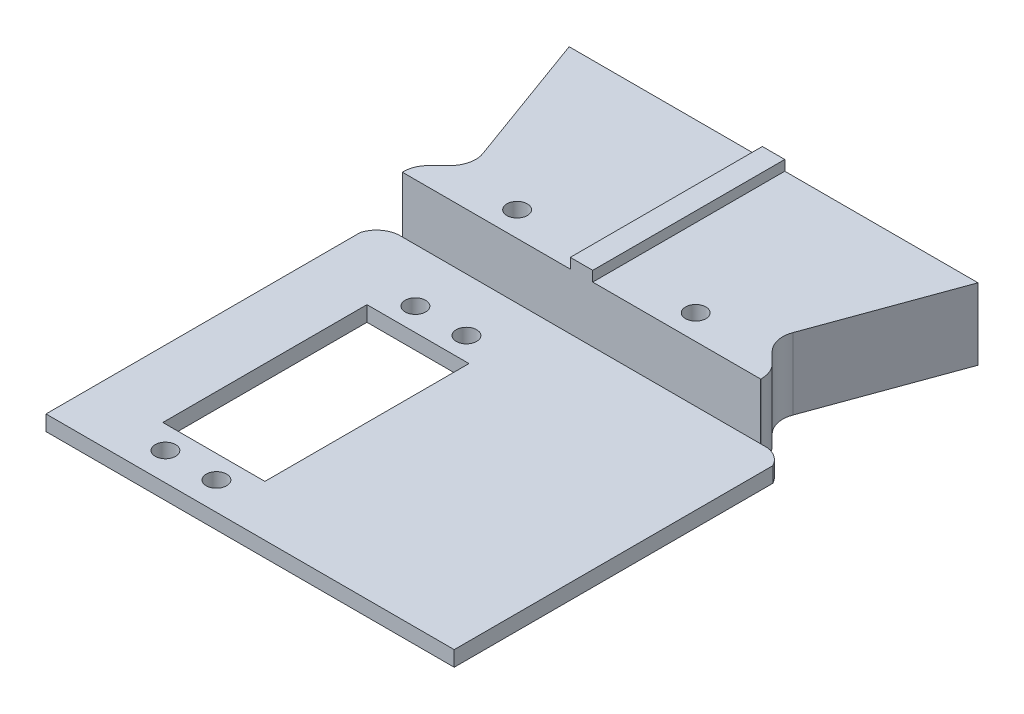
SolidWorks part; units mm, degrees
ref_plane "Front Plane" through (0, 0, 0) normal (0, 0, 1) x (1, 0, 0)
ref_plane "Top Plane" through (0, 0, 0) normal (0, 1, 0) x (1, 0, 0)
ref_plane "Right Plane" through (0, 0, 0) normal (1, 0, 0) x (0, 0, -1)
sketch "Sketch1" plane through (0, 0, 0) normal (0, 1, 0) x (1, 0, 0)
  line L0 (-17.5, 0) -> (17.5, 0) construction
  line L2 (-30.3893, 6.1749) -> (-40.0654, 32.76)
  line L3 (-40.0654, 32.76) -> (40.0654, 32.76)
  line L4 (40.0654, 32.76) -> (30.3893, 6.1749)
  line L5 (-35.1226, -23.3107) -> (-35.1226, -4.7122)
  line L6 (-35.1226, -23.3107) -> (35.1226, -23.3107)
  line L8 (-33.6581, -1.1767) -> (-31.5522, 0.9293)
  line L9 (35.1226, -23.3107) -> (35.1226, -4.7122)
  line L10 (33.6581, -1.1767) -> (31.5522, 0.9293)
  arc A2 (-31.5522, 0.9293) -> (-30.3893, 6.1749) centre (-35.0877, 4.4648) ccw
  arc A3 (-35.1226, -4.7122) -> (-33.6581, -1.1767) centre (-30.1226, -4.7122) cw
  arc A4 (35.1226, -4.7122) -> (33.6581, -1.1767) centre (30.1226, -4.7122) ccw
  arc A5 (31.5522, 0.9293) -> (30.3893, 6.1749) centre (35.0877, 4.4648) cw
  dimension "D5" = 5
  dimension "D6" = 5
  dimension "D7" = 18.5985
  dimension "D8" = 30.1226
  dimension "D19" = 5
  dimension "D20" = 5
  dimension "D1" = 35
  dimension "D2" = 17.5
  dimension "D3" = 23.3107
  dimension "D4" = 18.5985
  dimension "D9" = 30.1226
  dimension "D10" = 4.7122
  dimension "D11" = 5
  dimension "D12" = 32.76
  dimension "D13" = 70
  dimension "D14" = 70
  dimension "D15" = 28.2913
  dimension "D16" = 28.2913
  dimension "D17" = 2.9782
  dimension "D18" = 2.9782
extrude "Boss-Extrude1" add sketch "Sketch1" along normal blind 3
sketch "Sketch8" plane through (0, 3, 0) normal (0, 1, 0) x (1, 0, 0)
  line L0 (-35.1226, -23.3107) -> (35.1226, -23.3107) construction
  line L1 (-35.1226, -23.3107) -> (35.1226, -23.3107)
  line L2 (-35.1226, -23.3107) -> (-25.1226, -33.3107)
  line L3 (-25.1226, -33.3107) -> (25.1226, -33.3107)
  line L4 (25.1226, -33.3107) -> (35.1226, -23.3107)
  dimension "D1" = 10
  dimension "D2" = 45
  dimension "D3" = 45
extrude "Boss-Extrude5" add sketch "Sketch8" against normal blind 3
sketch "Croquis1" plane through (0, 3, 0) normal (0, 1, 0) x (1, 0, 0)
  line L0 (-40.0654, 32.76) -> (40.0654, 32.76) construction
  line L1 (0, 32.76) -> (0, 0) construction
  line L2 (0, 0) -> (-17.5, 0) construction
  line L3 (0, 0) -> (17.5, 0) construction
  circle A0 centre (-17.5, 0) radius 2
  circle A1 centre (17.5, 0) radius 2
  dimension "D4" = 4
  dimension "D5" = 4
  dimension "D1" = 32.76
  dimension "D2" = 17.5
  dimension "D3" = 17.5
extrude "Cortar-Extruir1" cut sketch "Croquis1" against normal blind 10
sketch "Croquis2" plane through (0, 3, 0) normal (0, 1, 0) x (1, 0, 0)
  line L1 (17, -36.0007) -> (40.0026, -36.0007)
  line L2 (40.0026, -36.0007) -> (40.0026, -33.0007)
  line L7 (17, -36.0007) -> (-40, -36.0007)
  line L8 (-40, -36.0007) -> (-40, -4.8773)
  line L9 (-40, -4.8773) -> (40.0026, -4.8773)
  line L10 (40.0026, -4.8773) -> (40.0026, -33.0007)
  line L13 (35.1226, -23.3107) -> (35.1226, -4.7122) construction
  dimension "D6" = 4.88
extrude "Saliente-Extruir1" add sketch "Croquis2" against normal up to surface (3 mm away) up to face at (-17.5, 0, 2)
sketch "Croquis3" plane through (0, 3, 0) normal (0, 1, 0) x (1, 0, 0)
  line L0 (-40, -4.8773) -> (-40, -36.0007) construction
  line L2 (40.0026, -36.0007) -> (40.0026, -4.8773) construction
  line L3 (40.0026, -4.8773) -> (35.1226, -4.8773) construction
  line L4 (40.0026, -36.0007) -> (40.0026, -4.8773)
  line L5 (40.0026, -4.8773) -> (35.1226, -4.8773)
  arc A0 (-35.1226, -4.8773) -> (-40, -9.3921) centre (-35.3039, -9.5734) ccw
  arc A1 (35.1226, -4.8773) -> (40.0026, -7.3959) centre (35.8131, -9.5263) cw
  line M1 (40.0026, -4.8773) -> (35.1226, -4.8773)
  dimension "D1" = 4.6996
  dimension "D2" = 4.7
extrude "Cortar-Extruir2" cut sketch "Croquis3" against normal blind 10 and the other way through all contours A1 L4 M1 region at (39.0792, 3, 5.5854)
sketch "Croquis4" plane through (0, 3, 0) normal (0, 1, 0) x (1, 0, 0)
  line L0 (-40, -4.8773) -> (-40, -36.0007) construction
  line L1 (-35.1226, -4.8773) -> (-40, -4.8773) construction
  line L2 (-35.1226, -4.8773) -> (-40, -4.8773)
  line L3 (-40, -4.8773) -> (-40, -36.0007)
  arc A0 (-35.1226, -4.8773) -> (-40, -8.2239) centre (-35.4947, -9.5625) ccw
  line M20 (-40, -4.8773) -> (-40, -36.0007)
  dimension "D1" = 4.7
extrude "Cortar-Extruir3" cut sketch "Croquis4" against normal blind 10 contours A0 L2 M20 region at (-38.9852, 3, 5.7663)
sketch "Croquis6" plane through (0, 3, 0) normal (0, 1, 0) x (1, 0, 0)
  line L0 (-35.1226, -4.8773) -> (35.1226, -4.8773)
  line L1 (-40.0654, 32.76) -> (-30.3893, 6.1749) construction
  line L2 (-31.5522, 0.9293) -> (-33.6581, -1.1767) construction
  line L3 (-40.0654, 32.76) -> (-30.3893, 6.1749)
  line L4 (-31.5522, 0.9293) -> (-33.6581, -1.1767)
  line L5 (33.6581, -1.1767) -> (31.5522, 0.9293) construction
  line L6 (30.3893, 6.1749) -> (40.0654, 32.76) construction
  line L7 (33.6581, -1.1767) -> (31.5522, 0.9293)
  line L8 (30.3893, 6.1749) -> (40.0654, 32.76)
  line L9 (35.1226, -4.8773) -> (35.1226, -4.7122) construction
  line L10 (35.1226, -4.8773) -> (35.1226, -4.7122)
  line L11 (-35.1226, -4.7122) -> (-35.1226, -4.8773) construction
  line L12 (-35.1226, -4.7122) -> (-35.1226, -4.8773)
  arc A0 (-31.5522, 0.9293) -> (-30.3893, 6.1749) centre (-35.0877, 4.4648) ccw construction
  arc A1 (-33.6581, -1.1767) -> (-35.1226, -4.7122) centre (-30.1226, -4.7122) ccw construction
  arc A2 (-31.5522, 0.9293) -> (-30.3893, 6.1749) centre (-35.0877, 4.4648) ccw
  arc A3 (-33.6581, -1.1767) -> (-35.1226, -4.7122) centre (-30.1226, -4.7122) ccw
  arc A4 (35.1226, -4.7122) -> (33.6581, -1.1767) centre (30.1226, -4.7122) ccw construction
  arc A5 (30.3893, 6.1749) -> (31.5522, 0.9293) centre (35.0877, 4.4648) ccw construction
  arc A6 (35.1226, -4.7122) -> (33.6581, -1.1767) centre (30.1226, -4.7122) ccw
  arc A7 (30.3893, 6.1749) -> (31.5522, 0.9293) centre (35.0877, 4.4648) ccw
  circle A8 centre (-16.7158, 19.9949) radius 9.4109
  circle M2 centre (17.5, 0) radius 2
  circle M3 centre (-17.5, 0) radius 2
  line M11 (35.1226, -4.8773) -> (35.1226, -4.7122)
  arc M12 (35.1226, -4.7122) -> (33.6581, -1.1767) centre (30.1226, -4.7122) ccw
  line M13 (33.6581, -1.1767) -> (31.5522, 0.9293)
  arc M14 (31.5522, 0.9293) -> (30.3893, 6.1749) centre (35.0877, 4.4648) cw
  line M15 (30.3893, 6.1749) -> (40.0654, 32.76)
  line M16 (40.0654, 32.76) -> (-40.0654, 32.76)
  line M17 (-40.0654, 32.76) -> (-30.3893, 6.1749)
  arc M18 (-30.3893, 6.1749) -> (-31.5522, 0.9293) centre (-35.0877, 4.4648) cw
  line M19 (-31.5522, 0.9293) -> (-33.6581, -1.1767)
  arc M20 (-33.6581, -1.1767) -> (-35.1226, -4.7122) centre (-30.1226, -4.7122) ccw
  line M21 (-35.1226, -4.7122) -> (-35.1226, -4.8773)
extrude "Saliente-Extruir2" add sketch "Croquis6" along normal blind 11 contours L0 A8 M21 M11 M12 M13 M14 M15 M16 M17 M18 M19 M20 M3 M2 | A8 region at (2.0372, 3, -14.179) region at (-16.7158, 3, -19.9949)
sketch "Croquis8" plane through (0, 0, 36.0007) normal (0, 0, 1) x (1, 0, 0)
  line L1 (-40, 3) -> (40.0026, 3)
  line L2 (-40, 3) -> (-40, 0)
  line L3 (-40, 0) -> (40.0026, 0)
  line L4 (40.0026, 3) -> (40.0026, 0)
extrude "Saliente-Extruir3" add sketch "Croquis8" along normal blind 33.83
sketch "Croquis9" plane through (0, 3, 0) normal (0, 1, 0) x (1, 0, 0)
  line L0 (-40, -69.8307) -> (0.0013, -69.8307) construction
  line L1 (40.0026, -69.8307) -> (-40, -69.8307) construction
  line L2 (0.0013, -69.8307) -> (0.0013, -29.8307) construction
  line L3 (0.0013, -29.8307) -> (-17.1, -29.8307) construction
  line L4 (-17.1, -29.8307) -> (-17.1, -12.8307) construction
  line L5 (-26.6, -66.8307) -> (-22.1, -66.8307) construction
  line L6 (-17.1, -66.8307) -> (-27.1, -66.8307)
  line L7 (-17.1, -66.8307) -> (-7.1, -66.8307)
  line L8 (-26.6, -66.8307) -> (-7.6, -66.8307)
  line L9 (-27.1, -66.8307) -> (-7.1, -66.8307)
  line L10 (-27.1, -59.8307) -> (-27.1, -19.8307)
  line L11 (-26.6, -12.8307) -> (-7.6, -12.8307)
  line L12 (-7.1, -59.8307) -> (-7.1, -19.8307)
  line L13 (-26.6, -66.8307) -> (-26.6, -59.8307)
  line L14 (-26.6, -59.8307) -> (-7.6, -59.8307)
  line L15 (-7.6, -66.8307) -> (-7.6, -59.8307)
  line L16 (-22.1, -66.8307) -> (-22.1, -64.3307) construction
  line L17 (-17.1, -66.8307) -> (-17.1, -59.8307) construction
  line L18 (-26.6, -12.8307) -> (-22.1, -12.8307) construction
  line L19 (-26.6, -12.8307) -> (-7.6, -12.8307)
  line L20 (-26.6, -12.8307) -> (-26.6, -19.8307)
  line L21 (-26.6, -19.8307) -> (-7.6, -19.8307)
  line L22 (-7.6, -12.8307) -> (-7.6, -19.8307)
  line L23 (-22.1, -12.8307) -> (-22.1, -15.3307) construction
  line L24 (-26.6, -59.8307) -> (-27.1, -59.8307)
  line L25 (-7.6, -59.8307) -> (-7.1, -59.8307)
  line L26 (-26.6, -19.8307) -> (-27.1, -19.8307)
  line L27 (-7.6, -19.8307) -> (-7.1, -19.8307)
  line L28 (-40, -8.2239) -> (-40, -69.8307) construction
  circle A0 centre (-17.1, -29.8307) radius 1.5
  circle A1 centre (-22.1, -64.3307) radius 2
  circle A2 centre (-12.1, -64.3307) radius 2
  circle A3 centre (-22.1, -15.3307) radius 2
  circle A4 centre (-12.1, -15.3307) radius 2
  point P18 (-26.6, -63.3307)
  dimension "D7" = 3
  dimension "D13" = 4
  dimension "D19" = 4
  dimension "D1" = 40
  dimension "D3" = 17
  dimension "D4" = 37
  dimension "D5" = 10
  dimension "D6" = 10
  dimension "D8" = 0.5
  dimension "D9" = 0.5
  dimension "D10" = 7
  dimension "D11" = 4.5
  dimension "D12" = 2.5
  dimension "D14" = 0.5
  dimension "D15" = 0.5
  dimension "D16" = 7
  dimension "D17" = 4.5
  dimension "D18" = 2.5
  dimension "D20" = 12.9
  dimension "D21" = 10
extrude "Cortar-Extruir7" cut sketch "Croquis9" against normal blind 33.83 contours L27 L21 L26 L10 L24 L14 L25 L12 A0 | A0 region at (-17.1, 3, 39.9199) region at (-17.1, 3, 29.8307)
extrude "Cortar-Extruir8" cut sketch "Croquis9<3>" against normal blind 33.83 contours A3 | A4 | A1 | A2 region at (-22.1, 3, 64.3307) region at (-12.1, 3, 64.3307) region at (-22.1, 3, 15.3307) region at (-12.1, 3, 15.3307)
sketch "Croquis9<3>" plane through (0, 3, 0) normal (0, 1, 0) x (1, 0, 0) same geometry as "Croquis9"
sketch "Croquis10" plane through (0, 14, 0) normal (0, 1, 0) x (1, 0, 0)
  line L0 (-35.1226, -4.8773) -> (35.1226, -4.8773) construction
  line L2 (-2.2, -4.8773) -> (2.2, -4.8773)
  line L5 (0, 0) -> (-2.2, 0.0027) construction
  line L6 (0, 0) -> (2.2, 0.0027) construction
  line L7 (-2.2, 0.0027) -> (2.2, 0.0027)
  line L8 (-2.2, -4.8773) -> (-2.2, 32.76)
  line L9 (-2.2, 32.76) -> (2.2, 32.76)
  line L10 (2.2, -4.8773) -> (2.2, 32.76)
  line L11 (40.0654, 32.76) -> (-40.0654, 32.76) construction
  line M5 (-35.1226, -4.8773) -> (35.1226, -4.8773)
  line M11 (40.0654, 32.76) -> (-40.0654, 32.76)
  dimension "D2" = 2.2
  dimension "D3" = 2.2
extrude "Saliente-Extruir4" add sketch "Croquis10" along normal blind 2 contours L7 L10 L8 M11 | L10 L7 L8 M5 region at (0, 14, 2.4373) region at (0, 14, -16.3814)
